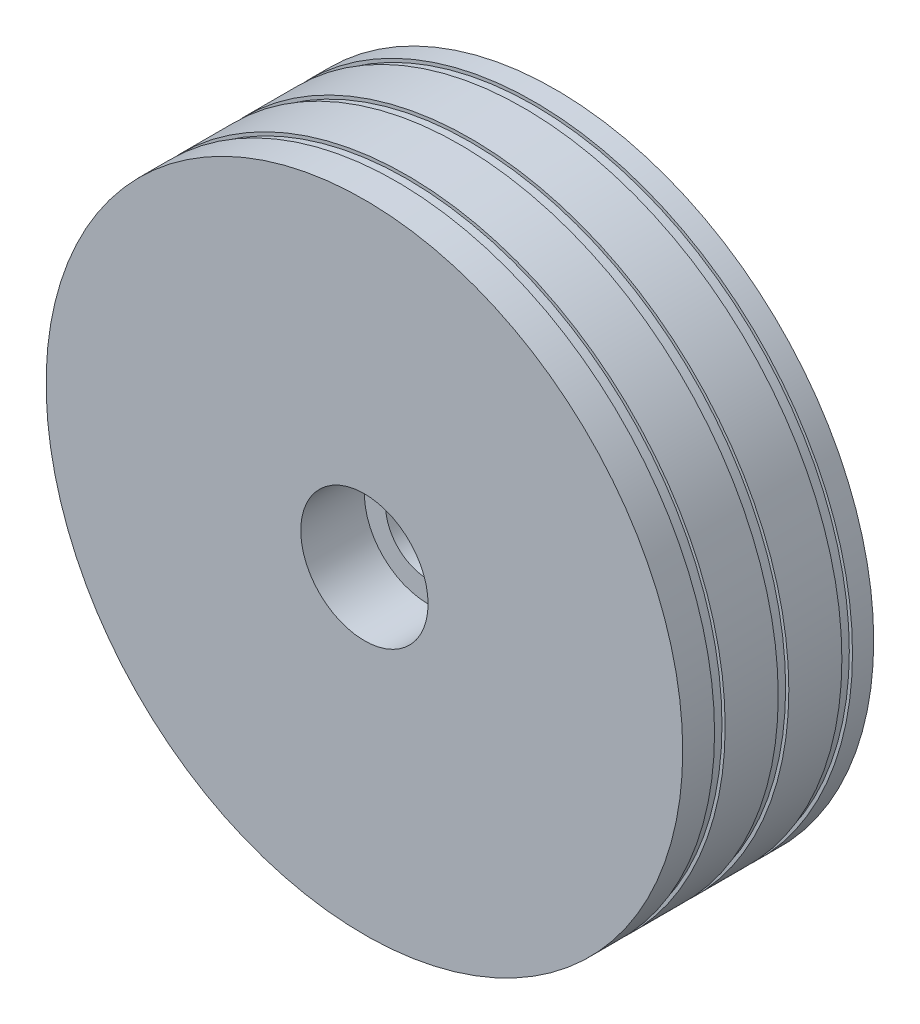
SolidWorks part; units mm, degrees
ref_plane "Front Plane" through (0, 0, 0) normal (0, 0, 1) x (1, 0, 0)
ref_plane "Top Plane" through (0, 0, 0) normal (0, 1, 0) x (1, 0, 0)
ref_plane "Right Plane" through (0, 0, 0) normal (1, 0, 0) x (0, 0, -1)
sketch "Sketch1" plane through (0, 0, 0) normal (0, 0, 1) x (1, 0, 0)
  circle A0 centre (0, 0) radius 15
  dimension "D1" = 30
extrude "Boss-Extrude1" add sketch "Sketch1" along normal blind 9
sketch "Sketch2" plane through (0, 0, 9) normal (0, 0, 1) x (1, 0, 0)
  circle A0 centre (0, 0) radius 2
  dimension "D1" = 4
extrude "Cut-Extrude1" cut sketch "Sketch2" against normal through all
sketch "Sketch3" plane through (0, 0, 9) normal (0, 0, 1) x (1, 0, 0)
  circle A0 centre (0, 0) radius 3
  dimension "D1" = 6
extrude "Cut-Extrude2" cut sketch "Sketch3" against normal blind 3
thread "Thread1" pitch 0.7 method extrude profile "Thread Profile1" start angle 0, offset 0, length 5, pitch 0.7, diameter 4
ref_plane "Plane1" through (2, 0, 0) normal (0, -1, 0) x (1, 0, 0)
sketch "Thread Profile1" plane through (2, 0, 0) normal (0, -1, 0) x (1, 0, 0)
  line L0 (0, 0) -> (0, 0.7) construction
  line L11 (0, 0) -> (0, 0.6125)
  line L12 (0, 0.6125) -> (-0.3789, 0.3937)
  line L13 (-0.3789, 0.3937) -> (-0.3789, 0.2187)
  line L15 (-0.3789, 0.2187) -> (0, 0)
  line L17 (-0.3789, 0.3062) -> (0, 0.3062) construction
  point P2 (0, 0)
  dimension "Pitch" = 0.7
  dimension "Profile_Angle" = 60
  dimension "Profile_Land" = 0.175
  dimension "Profile_Height" = 0.3789
ref_plane "Plane2" through (0, 0, 7.5) normal (0, 0, 1) x (1, 0, 0)
sketch "Sketch4" plane through (0, 0, 7.5) normal (0, 0, 1) x (1, 0, 0)
  circle A0 centre (0, 0) radius 14.85
  circle A1 centre (0, 0) radius 15
  dimension "D1" = 29.7
extrude "Cut-Extrude3" cut sketch "Sketch4" against normal blind 0.5
ref_plane "Plane3" through (0, 0, 4.5) normal (0, 0, 1) x (1, 0, 0)
sketch "Sketch5" plane through (0, 0, 4.5) normal (0, 0, 1) x (1, 0, 0)
  circle A0 centre (0, 0) radius 15
  circle A1 centre (0, 0) radius 14.85
  dimension "D1" = 29.7
extrude "Cut-Extrude4" cut sketch "Sketch5" against normal blind 0.5
ref_plane "Plane4" through (0, 0, 1.5) normal (0, 0, 1) x (1, 0, 0)
sketch "Sketch6" plane through (0, 0, 1.5) normal (0, 0, 1) x (1, 0, 0)
  circle A0 centre (0, 0) radius 15
  circle A1 centre (0, 0) radius 14.85
  dimension "D1" = 29.7
extrude "Cut-Extrude5" cut sketch "Sketch6" against normal blind 0.5
